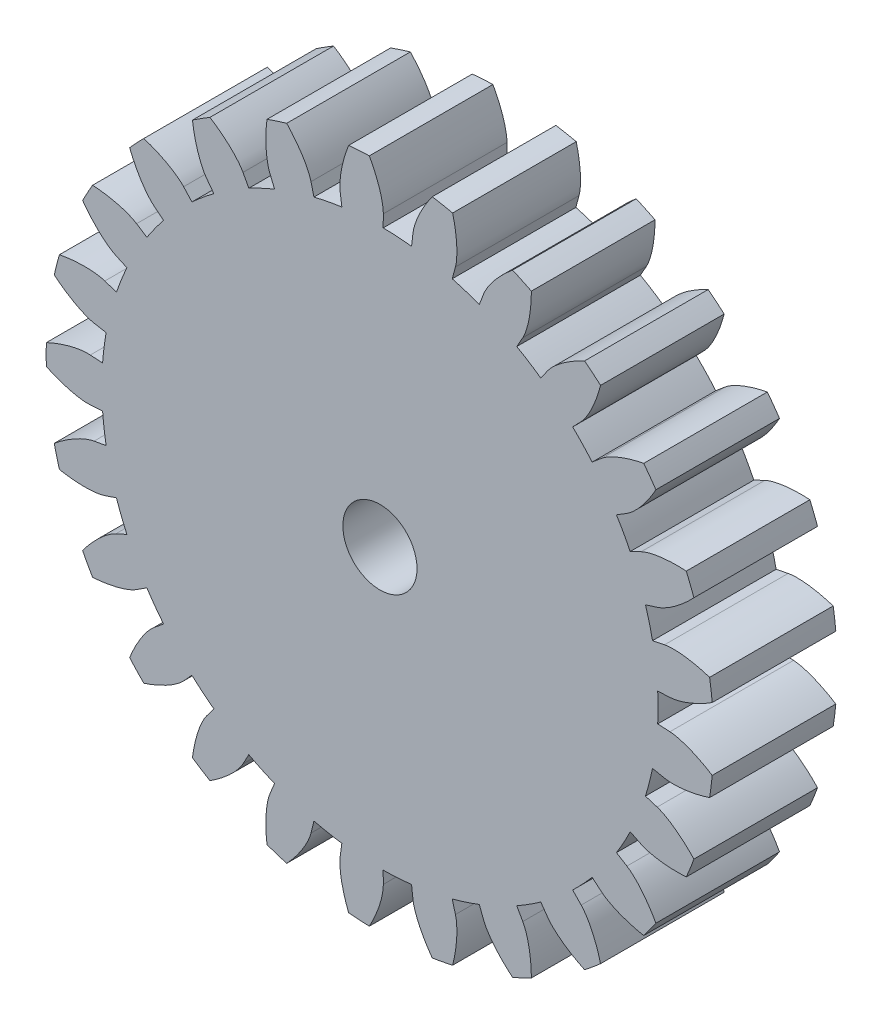
SolidWorks part; units mm, degrees
ref_plane "前视基准面" through (0, 0, 0) normal (0, 0, 1) x (1, 0, 0)
ref_plane "上视基准面" through (0, 0, 0) normal (0, 1, 0) x (1, 0, 0)
ref_plane "右视基准面" through (0, 0, 0) normal (1, 0, 0) x (0, 0, -1)
other "Configuration Table"
sketch "草图1" plane through (0, 0, 0) normal (0, 0, 1) x (1, 0, 0)
  line L0 (0, 0) -> (12.5, 0) construction
  line L1 (0, 0) -> (12.4753, 0.7849) construction
  line L2 (0, 0) -> (11.7308, 0.6006)
  line L3 (12.4753, 0.7849) -> (12.4753, -0.7849) construction
  line L4 (0, 0) -> (11.7308, -0.6006)
  circle A0 centre (0, 0) radius 13.5
  circle A1 centre (0, 0) radius 12.5 construction
  circle A2 centre (0, 0) radius 11.25
  circle A3 centre (0, 0) radius 11.7462 construction
  circle A4 centre (0, 0) radius 1.5
  spline S0 degree 4 poles (11.7308, 0.6006) (11.7755, 0.6029) (11.8643, 0.6116) (12.0316, 0.6433) (12.2735, 0.7093) (12.6814, 0.8559) (13.2995, 1.1611) (14.0704, 1.6798) (15.0324, 2.5516) (15.9945, 3.7303) (16.8544, 5.1636) (17.5588, 6.8208) (18.0528, 8.5514) (18.3481, 10.3262) (18.4616, 12.2104) (18.3582, 14.5457) (17.8786, 17.2961) (16.8605, 20.3774) (15.2143, 23.5842) (13.1252, 26.5195) (10.6599, 29.1451) (8.228, 31.1479) (5.9832, 32.6431) (4.0225, 33.738) (2.406, 34.5224) (0.7486, 35.2146) (-0.9455, 35.8144) (-3.0984, 36.4487) (-5.2958, 36.9294) (-7.181, 37.2087) (-8.7509, 37.3533) (-9.638, 37.4137) (-10.2546, 37.4438) (-10.8267, 37.4645) (-11.6179, 37.4744) (-12.1248, 37.4729) (-12.9482, 37.4584) (-13.5859, 37.4293) (-14.3618, 37.3861) (-15.0512, 37.329) (-15.7942, 37.2581) (-16.4973, 37.1736) (-17.0484, 37.1) (-17.3991, 37.0465) (-17.5812, 37.0186) knots 0 0 0 0 0 0.002802 0.005604 0.010661 0.015718 0.02996 0.048734 0.068727 0.096889 0.125051 0.153212 0.181374 0.209535 0.237696 0.271429 0.327752 0.384075 0.440398 0.496721 0.553044 0.609367 0.637529 0.66569 0.693852 0.722013 0.750174 0.778336 0.834659 0.86282 0.869861 0.876901 0.890982 0.900036 0.909091 0.920455 0.931818 0.943182 0.954545 0.965909 0.977273 0.988636 1 1 1 1 1 construction
  spline S1 degree 4 poles (11.7308, 0.6006) (11.7755, 0.6029) (11.8643, 0.6116) (12.0316, 0.6433) (12.2735, 0.7093) (12.6814, 0.8559) (13.2995, 1.1611) (14.0704, 1.6798) (15.0324, 2.5516) (15.9945, 3.7303) (16.8544, 5.1636) (17.5588, 6.8208) (18.0528, 8.5514) (18.3481, 10.3262) (18.4616, 12.2104) (18.3582, 14.5457) (17.8786, 17.2961) (16.8605, 20.3774) (15.2143, 23.5842) (13.1252, 26.5195) (10.6599, 29.1451) (8.228, 31.1479) (5.9832, 32.6431) (4.0225, 33.738) (2.406, 34.5224) (0.7486, 35.2146) (-0.9455, 35.8144) (-3.0984, 36.4487) (-5.2958, 36.9294) (-7.181, 37.2087) (-8.7509, 37.3533) (-9.638, 37.4137) (-10.2546, 37.4438) (-10.8267, 37.4645) (-11.4114, 37.4718) (-11.6764, 37.473) (-11.8076, 37.4728) knots 0 0 0 0 0 0.002802 0.005604 0.010661 0.015718 0.02996 0.048734 0.068727 0.096889 0.125051 0.153212 0.181374 0.209535 0.237696 0.271429 0.327752 0.384075 0.440398 0.496721 0.553044 0.609367 0.637529 0.66569 0.693852 0.722013 0.750174 0.778336 0.834659 0.86282 0.869861 0.876901 0.890982 0.900036 0.909091 0.909091 0.909091 0.909091 0.909091
  spline S2 degree 4 poles (11.7308, -0.6006) (11.7755, -0.6029) (11.8643, -0.6116) (12.0316, -0.6433) (12.2735, -0.7093) (12.6814, -0.8559) (13.2995, -1.1611) (14.0704, -1.6798) (15.0324, -2.5516) (15.9945, -3.7303) (16.8544, -5.1636) (17.5588, -6.8208) (18.0528, -8.5514) (18.3481, -10.3262) (18.4616, -12.2104) (18.3582, -14.5457) (17.8786, -17.2961) (16.8605, -20.3774) (15.2143, -23.5842) (13.1252, -26.5195) (10.6599, -29.1451) (8.228, -31.1479) (5.9832, -32.6431) (4.0225, -33.738) (2.406, -34.5224) (0.7486, -35.2146) (-0.9455, -35.8144) (-3.0984, -36.4487) (-5.2958, -36.9294) (-7.181, -37.2087) (-8.7509, -37.3533) (-9.638, -37.4137) (-10.2546, -37.4438) (-10.8267, -37.4645) (-11.6179, -37.4744) (-12.1248, -37.4729) (-12.9482, -37.4584) (-13.5859, -37.4293) (-14.3618, -37.3861) (-15.0512, -37.329) (-15.7942, -37.2581) (-16.4973, -37.1736) (-17.0484, -37.1) (-17.3991, -37.0465) (-17.5812, -37.0186) knots 0 0 0 0 0 0.002802 0.005604 0.010661 0.015718 0.02996 0.048734 0.068727 0.096889 0.125051 0.153212 0.181374 0.209535 0.237696 0.271429 0.327752 0.384075 0.440398 0.496721 0.553044 0.609367 0.637529 0.66569 0.693852 0.722013 0.750174 0.778336 0.834659 0.86282 0.869861 0.876901 0.890982 0.900036 0.909091 0.920455 0.931818 0.943182 0.954545 0.965909 0.977273 0.988636 1 1 1 1 1 construction
  spline S3 degree 4 poles (11.7308, -0.6006) (11.7755, -0.6029) (11.8643, -0.6116) (12.0316, -0.6433) (12.2735, -0.7093) (12.6814, -0.8559) (13.2995, -1.1611) (14.0704, -1.6798) (15.0324, -2.5516) (15.9945, -3.7303) (16.8544, -5.1636) (17.5588, -6.8208) (18.0528, -8.5514) (18.3481, -10.3262) (18.4616, -12.2104) (18.3582, -14.5457) (17.8786, -17.2961) (16.8605, -20.3774) (15.2143, -23.5842) (13.1252, -26.5195) (10.6599, -29.1451) (8.228, -31.1479) (5.9832, -32.6431) (4.0225, -33.738) (2.406, -34.5224) (0.7486, -35.2146) (-0.9455, -35.8144) (-3.0984, -36.4487) (-5.2958, -36.9294) (-7.181, -37.2087) (-8.7509, -37.3533) (-9.638, -37.4137) (-10.2546, -37.4438) (-10.8267, -37.4645) (-11.4114, -37.4718) (-11.6764, -37.473) (-11.8076, -37.4728) knots 0 0 0 0 0 0.002802 0.005604 0.010661 0.015718 0.02996 0.048734 0.068727 0.096889 0.125051 0.153212 0.181374 0.209535 0.237696 0.271429 0.327752 0.384075 0.440398 0.496721 0.553044 0.609367 0.637529 0.66569 0.693852 0.722013 0.750174 0.778336 0.834659 0.86282 0.869861 0.876901 0.890982 0.900036 0.909091 0.909091 0.909091 0.909091 0.909091
  point P15 (12.4753, 0)
  dimension "齿顶圆直径" = 27
  dimension "分度圆直径" = 25
  dimension "齿根圆直径" = 22.5
  dimension "基圆直径" = 23.4923
  dimension "内孔直径" = 3
  dimension "渐近线镜像线夹角" = 3.6
extrude "凸台-拉伸1" add sketch "草图1" along normal blind 5 contours A0 | A4
extrude "切除-拉伸1" cut sketch "草图1<3>" along normal through all contours A2 S3 A0 S1 region at (12.5298, 0, 0)
sketch "草图1<3>" plane through (0, 0, 0) normal (0, 0, 1) x (1, 0, 0) same geometry as "草图1"
pattern_circular "阵列(圆周)1" count 25 every 14.4 about axis through (0, 0, 5) along (0, 0, 1) of "切除-拉伸1"
equation "\"m\"= 1'模数"
equation "\"z\"= 25'齿数"
equation "\"a\"= 20度'压力角"
equation "\"d\"= \"m\" * \"z\"'分度圆直径"
equation "\"da\"= ( \"z\" + 2 ) * \"m\"'齿顶圆直径"
equation "\"df\"= ( \"z\" - 2.5 ) * \"m\"'齿根圆直径"
equation "\"s\"= 0.5 * PI * \"m\"'分度圆齿厚"
equation "\"r\"= 0.38 * \"m\"'齿根圆角"
equation "\"B\"= 0.3 * \"d\"'齿厚"
equation "\"db\"= \"m\" * \"z\" * cos ( \"a\" )'基圆直径"
equation "\"rb\"= \"db\" / 2'基圆半径"
equation "\"齿顶圆直径@草图1\"= \"da\""
equation "\"分度圆直径@草图1\"= \"d\""
equation "\"齿根圆直径@草图1\"= \"df\""
equation "\"基圆直径@草图1\"= \"db\""
equation "\"渐近线镜像线夹角@草图1\"= 360 / 4 / \"z\""
equation "\"h\"= 5'齿轮厚度"
equation "\"ir\"= 3'内孔直径"
equation "\"内孔直径@草图1\"= \"ir\""
equation "\"齿轮厚@凸台-拉伸1\"= \"h\""
equation "\"齿轮夹角@阵列(圆周)1\"= 360 / \"z\""
equation "\"齿数@阵列(圆周)1\"= \"z\""
